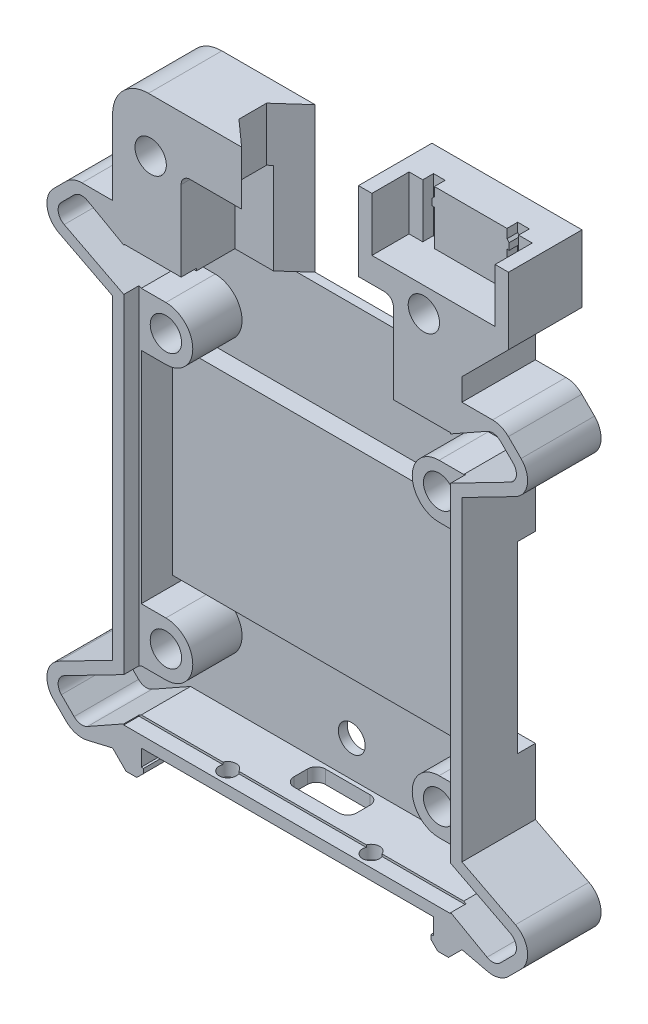
SolidWorks part; units mm, degrees
ref_plane "Front Plane" through (0, 0, 0) normal (0, 0, 1) x (1, 0, 0)
ref_plane "Top Plane" through (0, 0, 0) normal (0, 1, 0) x (1, 0, 0)
ref_plane "Right Plane" through (0, 0, 0) normal (1, 0, 0) x (0, 0, -1)
sketch "Sketch1" plane through (0, 0, 0) normal (0, 0, 1) x (1, 0, 0)
  line L0 (15.25, -20.35) -> (18, -20.35)
  line L1 (-19.5, -32.6) -> (19.5, -32.6)
  line L2 (-19.5, -32.6) -> (-19.5, 31.1)
  line L3 (-19.5, 31.1) -> (19.5, 31.1)
  line L4 (19.5, -32.6) -> (19.5, 31.1)
  line L5 (-15.25, -20.35) -> (-18, -20.35)
  line L6 (15.25, -26.35) -> (18, -26.35)
  line L7 (6.95, 31.1) -> (-15.5, 31.1) construction
  line L8 (-18, -31.1) -> (-18, 29.6)
  line L9 (-18, 29.6) -> (18, 29.6)
  line L10 (18, -31.1) -> (18, 29.6)
  line L11 (-18, -31.1) -> (18, -31.1)
  line L12 (-18, 14.9) -> (18, 14.9)
  line L13 (7.85, 14.9) -> (-4.95, 14.9) construction
  line L14 (-15.25, 4.15) -> (-18, 4.15)
  line L15 (-15.25, 10.15) -> (-18, 10.15)
  line L16 (15.25, 10.15) -> (18, 10.15)
  line L17 (15.25, 4.15) -> (18, 4.15)
  line L18 (-15.25, -26.35) -> (-18, -26.35)
  line L19 (19.5, -32.6) -> (19.5, -18.35) construction
  line L20 (-19.5, -32.6) -> (-19.5, -18.35) construction
  line L21 (19.5, -32.6) -> (-19.5, -32.6) construction
  line L22 (0, 31.1) -> (0, -32.6) construction
  line L23 (9.45, 26.9) -> (24.7, 26.9)
  line L24 (9.45, 26.9) -> (9.45, 33.9)
  line L25 (9.45, 33.9) -> (24.7, 33.9)
  line L26 (24.7, 26.9) -> (24.7, 33.9)
  line L27 (18, 29.6) -> (19.5, 31.1) construction
  line L28 (18.75, 30.35) -> (0, 30.35) construction
  line L29 (9.45, 26.9) -> (7.95, 26.9) construction
  line L30 (-7.95, 31.1) -> (7.95, 31.1)
  line L31 (-7.95, 31.1) -> (-7.95, 29.6)
  line L32 (-7.95, 29.6) -> (7.95, 29.6)
  line L33 (7.95, 31.1) -> (7.95, 29.6)
  line L34 (-7.95, 31.1) -> (7.95, 29.6) construction
  line L35 (-7.95, 29.6) -> (7.95, 31.1) construction
  line L36 (7.95, 26.9) -> (7.95, 29.6) construction
  line L37 (18, 29.6) -> (19.5, 29.6) construction
  line L38 (24.7, 26.4) -> (19.5, 21.2)
  line L39 (9.45, 33.9) -> (7.95, 33.9)
  line L40 (23.2, 33.9) -> (23.2, 26.9)
  line L41 (7.95, 33.9) -> (7.95, 31.1)
  line L42 (24.7, 30.4) -> (23.2, 30.4) construction
  line L43 (24.7, 26.9) -> (19.5, 26.9)
  line L44 (24.7, 26.9) -> (24.7, 26.4)
  line L45 (24.7, 26.4) -> (19.5, 26.4)
  line L46 (19.5, 26.9) -> (19.5, 26.4)
  circle A0 centre (15.25, -23.35) radius 1.75
  arc A1 (-15.5, 31.1) -> (-19.5, 27.1) centre (-15.5, 27.1) ccw construction
  circle A2 centre (15.25, -23.35) radius 3
  arc A3 (-15.5, 31.1) -> (-19.5, 27.1) centre (-15.5, 27.1) ccw
  arc A4 (-15.5, 29.6) -> (-18, 27.1) centre (-15.5, 27.1) ccw
  circle A6 centre (-15.25, -23.35) radius 1.75
  circle A7 centre (-15.25, -23.35) radius 1.75
  circle A8 centre (-15.25, 7.15) radius 1.75
  circle A9 centre (15.25, 7.15) radius 1.75
  circle A10 centre (15.25, 25.15) radius 1.75
  circle A11 centre (-15.25, 25.15) radius 1.75
  circle A12 centre (-15.25, -23.35) radius 3
  circle A13 centre (-15.25, -23.35) radius 3
  circle A14 centre (15.25, 7.15) radius 3
  circle A15 centre (-15.25, 7.15) radius 3
  dimension "D2" = 1.5
  dimension "D4" = 6
  dimension "D3" = 3.5
  dimension "D5" = 13.75
  dimension "D6" = 15.9
  dimension "D7" = 7
  dimension "D8" = 45
  dimension "D9" = 0.5
  dimension "D1" = 1.5
extrude "Base shape" add sketch "Sketch1" along normal up to surface (8.2 mm away) contours A15 L8 L9 L31 L3 A3 L2 L1 L4 L23 L10 A14 A2 L11 A12 | A12 L8 L18 | A12 L8 A6 | L8 A12 | A12 L5 L8 | A15 L8 L14 | A15 L8 A8 | L8 A15 | A15 L15 L8 | L23 A10 L24 L9 A4 L8 L12 L10 A11 | A4 L9 L8 | L33 L3 L31 L9 | L3 L33 L9 L24 | L24 L9 L10 L23 L4 L3 | L24 L23 L10 L9 | A14 L10 L16 | L10 A14 A9 | A14 L17 L10 | L10 A14 | L10 A2 L6 | A2 L10 A0 | L0 A2 L10 | A2 L10 | L40 L25 L24 L3 L4 L23 | L25 L40 L23 L26 | L38 L45 L4 | L45 L44 L23 L4 | L39 L41 L3 L24 region at (16.8481, -20.9099, 0) region at (17.3601, -20.8437, 0) region at (18.7469, -8.1, 0) region at (17.3601, -25.8563, 0) region at (18.1004, -23.35, 0) region at (17.3601, 4.6437, 0) region at (16.8481, 4.7099, 0) region at (18.1004, 7.15, 0) region at (17.3601, 9.6563, 0) region at (-17.3601, -25.8563, 0) region at (-0.6044, 21.831, 0) region at (-18.1004, -23.35, 0) region at (-17.9169, -23.35, 0) region at (13.725, 28.25, 0) region at (15.3803, 29.9053, 0) region at (-17.3601, -20.8437, 0) region at (22.1, 26.65, 0) region at (17.77, 31.4935, 0) region at (-17.3601, 9.6563, 0) region at (-17.4416, 29.0416, 0) region at (8.7, 30.35, 0) region at (21.2333, 24.6667, 0) region at (23.95, 30.4, 0) region at (-16.8481, 9.5901, 0) region at (-18.1004, 7.15, 0) region at (-17.3601, 4.6437, 0) region at (0, 30.35, 0) region at (8.7, 32.5, 0)
sketch "Sketch3" plane through (19.5, 0, 0) normal (1, 0, 0) x (0, 0, -1)
  line L1 (0, -18.35) -> (-2, -18.35)
  line L2 (0, -18.35) -> (0, 2.15)
  line L3 (0, 2.15) -> (-2, 2.15)
  line L4 (-2, -18.35) -> (-2, 2.15)
  line L5 (0, -18.35) -> (1.75, -18.35) construction
  line L6 (0, 2.15) -> (1.75, 2.15) construction
  line L7 (0, -32.6) -> (0, 21.2) construction
  dimension "D1" = 2
extrude "Strap cut" cut sketch "Sketch3" against normal through all
sketch "Sketch4" plane through (0, 31.1, 0) normal (0, 1, 0) x (1, 0, 0)
  line L2 (7.95, 0) -> (-5.0998, 0)
  line L4 (-15.5, 0) -> (7.95, 0) construction
  line L5 (-15.5, -8.2) -> (7.95, -8.2) construction
  line L6 (7.95, -8.2) -> (-5.0998, -8.2)
  line L12 (7.95, -8.3) -> (7.95, 0.1)
  line L13 (7.95, 0.1) -> (-4.9883, 0.1)
  line L14 (-4.9883, 0.1) -> (-7.95, -2.5553)
  line L15 (-7.95, -2.5553) -> (-7.95, -5.6447)
  line L16 (-7.95, -5.6447) -> (-4.9883, -8.3)
  line L17 (-4.9883, -8.3) -> (7.95, -8.3)
  line L18 (7.95, -8.3) -> (7.95, 0.1)
  line L19 (7.95, 0.1) -> (-4.9883, 0.1)
  line L20 (-4.9883, 0.1) -> (-7.95, -2.5553)
  line L21 (-7.95, -2.5553) -> (-7.95, -5.6447)
  line L22 (-7.95, -5.6447) -> (-4.9883, -8.3)
  line L23 (-4.9883, -8.3) -> (7.95, -8.3)
  dimension "D1" = 0.1
extrude "XT60 cut" cut sketch "Sketch4" against normal up to next contours L21 L22 L18 L20 region at (0.4142, 31.1, 4.1)
sketch "Sketch6" plane through (0, 0, 8.2) normal (0, 0, 1) x (1, 0, 0)
  line L0 (8.85, 14.9) -> (10.85, 14.9) construction
  line L1 (11.85, 24.1) -> (11.85, 15.9) construction
  line L3 (-11.85, 14.9) -> (11.85, 14.9)
  line L4 (-11.85, 24.1) -> (-11.85, 15.9) construction
  line L5 (11.85, 24.1) -> (11.85, 15.9)
  line L6 (10.85, 25.1) -> (-10.85, 25.1)
  line L7 (-11.85, 24.1) -> (-11.85, 15.9)
  line L8 (-11.85, 15.9) -> (-11.85, 14.9)
  line L9 (11.85, 15.9) -> (11.85, 14.9)
  arc A2 (-10.85, 25.1) -> (-11.85, 24.1) centre (-10.85, 24.1) ccw construction
  arc A3 (-10.85, 25.1) -> (-11.85, 24.1) centre (-10.85, 24.1) ccw
  arc A4 (11.85, 24.1) -> (10.85, 25.1) centre (10.85, 24.1) ccw construction
  arc A5 (11.85, 24.1) -> (10.85, 25.1) centre (10.85, 24.1) ccw
  line M1 (7.95, 33.9) -> (7.95, 14.9)
  line M15 (-5.0998, 14.9) -> (-5.0998, 31.1)
  line M118 (7.95, 14.9) -> (18, 14.9)
  line M134 (-18, 14.9) -> (-5.0998, 14.9)
extrude "IO wires cut" cut sketch "Sketch6" against normal blind 6 contours L7 L8 M134 M15 | L3 M15 M1 | L5 L9 M1 M118 region at (-8.465, 19.9848, 8.2) region at (1.4251, 20, 8.2) region at (9.8906, 19.9735, 8.2)
sketch "Sketch7" plane through (-18, 0, 0) normal (1, 0, 0) x (0, 0, -1)
  line L6 (0, -18.35) -> (0, -20.35)
  line L7 (-2, -18.35) -> (0, -18.35)
  line L8 (-2, 2.15) -> (-2, -18.35)
  line L9 (0, 2.15) -> (-2, 2.15)
  line L12 (0, 3.15) -> (-3, 3.15)
  line L13 (-3, 3.15) -> (-3, -19.35)
  line L14 (-3, -19.35) -> (-1, -19.35)
  line L15 (-1, -19.35) -> (-1, -20.35)
  line L16 (-1, -20.35) -> (0, -20.35)
  line L17 (0, 3.15) -> (-1, 3.15)
  line L19 (0, -31.1) -> (-1, -31.1)
  line L22 (0, -31.1) -> (0, -20.35)
  line L23 (0, -20.35) -> (-1, -20.35)
  line L24 (-1, -31.1) -> (-1, -20.35)
  line L25 (0, 3.15) -> (0, 14.9)
  line L26 (0, 14.9) -> (-1, 14.9)
  line L27 (-1, 3.15) -> (-1, 14.9)
  line L28 (-8.2, 14.9) -> (0, 14.9) construction
  line L31 (0, -20.35) -> (0, -18.35) construction
  line L32 (0, 2.15) -> (-2, 2.15) construction
  line M48 (0, -20.35) -> (0, -18.35)
  line M49 (0, -18.35) -> (-2, -18.35)
  line M50 (-2, -18.35) -> (-2, 2.15)
  line M51 (-2, 2.15) -> (0, 2.15)
  line M52 (0, 2.15) -> (0, 4.15)
  line M53 (0, 4.15) -> (-8.2, 4.15)
  line M55 (-8.2, -20.35) -> (0, -20.35)
  dimension "D1" = 1
extrude "Bottom" add sketch "Sketch7" along normal up to surface (36 mm away) contours L27 L25 L26 M53 | L27 L12 M52 M53 | L14 L15 L12 L13 M55 M48 M49 M50 M51 M52 | L24 L19 L22 M55 region at (-18, -8.5273, 2.2091) region at (-18, -25.725, 0.5) region at (-18, 3.65, 0.5) region at (-18, 9.525, 0.5) up to face at (18, -8.1, 2.55)
sketch "Sketch9" plane through (0, 0, 0) normal (0, 0, -1) x (-1, 0, 0)
  circle A0 centre (15.25, -23.35) radius 1.75 construction
  circle A1 centre (-15.25, 7.15) radius 1.75 construction
  circle A2 centre (15.25, 7.15) radius 1.75 construction
  circle A3 centre (15.25, -23.35) radius 1.75 construction
  circle A4 centre (15.25, -23.35) radius 1.75
  circle A5 centre (-15.25, 7.15) radius 1.75
  circle A6 centre (15.25, 7.15) radius 1.75
  circle A7 centre (15.25, -23.35) radius 1.75
  circle A8 centre (-15.25, -23.35) radius 1.75 construction
  circle A9 centre (-15.25, -23.35) radius 1.75
extrude "Bottom holes" cut sketch "Sketch9" against normal up to next contours A5 | A6 | A4 | A9 region at (-15.25, -23.35, 0) region at (15.25, 7.15, 0) region at (-15.25, 7.15, 0) region at (15.25, -23.35, 0)
sketch "Sketch8" plane through (0, 0, 8.2) normal (0, 0, 1) x (1, 0, 0)
  line L1 (-18, 14.9) -> (18, -31.1) construction
  line L3 (-18.25, -31.35) -> (18.25, -31.35)
  line L4 (-18.25, -31.35) -> (-18.25, 15.15)
  line L5 (-18.25, 15.15) -> (18.25, 15.15)
  line L6 (18.25, -31.35) -> (18.25, 15.15)
  line L7 (-18.25, -31.35) -> (18.25, 15.15) construction
  line L8 (-18.25, 15.15) -> (18.25, -31.35) construction
  line L10 (-18, 10.15) -> (-18, 14.9) construction
  line L11 (-18, 14.9) -> (-18.25, 14.9) construction
  line L12 (-18, 14.9) -> (-18, 15.15) construction
  point P2 (0, -8.1)
  point P7 (0, 0)
  dimension "D1" = 0.25
extrude "PCB cut" cut sketch "Sketch8" against normal blind 1.7
sketch "Sketch11" plane through (0, -32.6, 0) normal (0, -1, 0) x (1, 0, 0)
  line L0 (19.5, 8.2) -> (19.5, 0) construction
  line L1 (-19.5, 8.2) -> (19.5, 8.2)
  line L2 (-19.5, 8.2) -> (-19.5, -1.8)
  line L3 (-19.5, -1.8) -> (19.5, -1.8)
  line L4 (19.5, 8.2) -> (19.5, -1.8)
  line L5 (-19.5, 3.2) -> (19.5, 3.2) construction
  line L6 (0, -1.8) -> (0, 8.2) construction
  line L8 (-2.5, 4.95) -> (2.5, 4.95)
  line L9 (-3.5, 3.95) -> (-3.5, 2.45)
  line L10 (-2.5, 1.45) -> (2.5, 1.45)
  line L11 (3.5, 3.95) -> (3.5, 2.45)
  line L12 (-3.5, 4.95) -> (3.5, 1.45) construction
  line L13 (-3.5, 1.45) -> (3.5, 4.95) construction
  arc A0 (2.5, 4.95) -> (3.5, 3.95) centre (2.5, 3.95) cw
  arc A1 (2.5, 1.45) -> (3.5, 2.45) centre (2.5, 2.45) ccw
  arc A2 (-3.5, 2.45) -> (-2.5, 1.45) centre (-2.5, 2.45) ccw
  arc A3 (-2.5, 4.95) -> (-3.5, 3.95) centre (-2.5, 3.95) ccw
  point P11 (0, 3.2)
  dimension "D4" = 1
  dimension "D1" = 10
  dimension "D2" = 7
  dimension "D3" = 3.5
extrude "Ledbar wires cut" cut sketch "Sketch11" against normal up to next contours L8 A3 L9 A2 L10 A1 L11 A0 region at (0, -32.6, 3.2)
sketch "Sketch13" plane through (0, -32.6, 0) normal (0, -1, 0) x (1, 0, 0)
  line L0 (-19.5, 8.2) -> (19.5, 8.2) construction
  line L1 (19.5, 0) -> (16.3, 0)
  line L2 (19.5, 0) -> (19.5, 8.2)
  line L3 (19.5, 8.2) -> (16.3, 8.2)
  line L4 (16.3, 0) -> (16.3, 8.2)
  line L5 (16.1, -1.8) -> (16.1, 8.2) construction
  line L6 (0, 8.2) -> (0, 0) construction
  line L7 (-19.5, 0) -> (-16.3, 0)
  line L8 (-19.5, 0) -> (-19.5, 8.2)
  line L9 (-19.5, 8.2) -> (-16.3, 8.2)
  line L10 (-16.3, 0) -> (-16.3, 8.2)
  dimension "D1" = 0.2
extrude "Ledbar sides" add sketch "Sketch13" along normal blind 1.6
sketch "Sketch16" plane through (0, 33.9, 0) normal (0, 1, 0) x (1, 0, 0)
  line L0 (7.95, -6.125) -> (24.7, -6.125) construction
  line L1 (7.95, -8.2) -> (24.7, -8.2) construction
  line L2 (21.675, -2.85) -> (20.375, -2.85)
  line L3 (20.375, -4.05) -> (20.375, -2.85)
  line L4 (9.45, -4.05) -> (23.2, -4.05)
  line L5 (9.45, -4.05) -> (9.45, -8.2)
  line L6 (9.45, -8.2) -> (23.2, -8.2)
  line L7 (23.2, -4.05) -> (23.2, -8.2)
  line L8 (9.45, -4.05) -> (23.2, -8.2) construction
  line L9 (9.45, -8.2) -> (23.2, -4.05) construction
  line L10 (24.7, -8.2) -> (24.7, 0) construction
  line L11 (7.95, -8.2) -> (7.95, 0) construction
  line L12 (16.325, -8.2) -> (16.325, -4.05) construction
  line L13 (11.625, -2.85) -> (11.625, -4.05) construction
  line L14 (10.975, -4.05) -> (12.275, -4.05)
  line L15 (10.975, -4.05) -> (10.975, -2.85)
  line L16 (10.975, -2.85) -> (12.275, -2.85)
  line L17 (12.275, -4.05) -> (12.275, -2.85)
  line L18 (10.975, -2.85) -> (10.975, -8.2) construction
  line L19 (21.675, -4.05) -> (21.675, -2.85)
  point P6 (16.325, -6.125)
  dimension "D1" = 13.75
  dimension "D2" = 4.15
  dimension "D3" = 1.3
  dimension "D4" = 1.2
  dimension "D5" = 4.7
extrude "Balance plug cut" cut sketch "Sketch16" against normal blind 6 contours L7 L4 L5 L6 | L4 L17 L16 L15 | L4 L19 L2 L3 region at (21.025, 33.9, 3.45) region at (16.325, 33.9, 6.125) region at (11.625, 33.9, 3.45)
sketch "Sketch17" plane through (0, 0, 2.85) normal (0, 0, 1) x (1, 0, 0)
  line L0 (16.325, 33.9) -> (16.325, 27.9) construction
  line L1 (12.275, 33.9) -> (20.375, 33.9) construction
  line L2 (12.275, 27.9) -> (20.375, 27.9) construction
  line L3 (12.275, 27.9) -> (12.275, 33.9) construction
  line L4 (12.025, 32.9) -> (20.625, 32.9)
  line L5 (12.025, 32.9) -> (12.025, 31.9)
  line L6 (12.025, 31.9) -> (20.625, 31.9)
  line L7 (20.625, 32.9) -> (20.625, 31.9)
  line L8 (12.025, 32.9) -> (20.625, 31.9) construction
  line L9 (12.025, 31.9) -> (20.625, 32.9) construction
  line L10 (12.025, 32.65) -> (12.275, 32.9)
  line L11 (20.625, 32.65) -> (20.375, 32.9)
  point P6 (16.325, 32.4)
  line M7 (20.375, 33.9) -> (20.375, 27.9)
  dimension "D1" = 0.25
  dimension "D2" = 1
  dimension "D3" = 1
  dimension "D4" = 45
extrude "Balance plug locks" add sketch "Sketch17" along normal up to surface (1.2 mm away) contours L10 L5 L6 L4 M7 | L7 L11 L6 M7 region at (16.2154, 32.3984, 2.85) region at (20.494, 32.3405, 2.85) up to face at (16.325, 30.9, 4.05)
sketch "Sketch18" plane through (0, 0, 0) normal (0, 0, -1) x (-1, 0, 0)
  line L0 (0, -32.6) -> (0, -18.35) construction
  line L1 (16.3, -32.6) -> (-16.3, -32.6) construction
  line L2 (19.5, -18.35) -> (-19.5, -18.35) construction
  line L3 (-19.5, -28.6) -> (19.5, -28.6) construction
  line L4 (-19.5, -34.2) -> (-19.5, -18.35) construction
  line L5 (19.5, -34.2) -> (19.5, -18.35) construction
  circle A0 centre (0, -27.1) radius 1.5
  dimension "D2" = 3
  dimension "D1" = 4
extrude "PDB removal hole" cut sketch "Sketch18" against normal up to next
sketch "Sketch14" plane through (0, -32.6, 0) normal (0, -1, 0) x (1, 0, 0)
  circle A0 centre (8, 6.85) radius 0.95
  circle A1 centre (-8, 6.85) radius 0.95
  dimension "D1" = 1.9
extrude "Ledbar holes" cut sketch "Sketch14" against normal up to next
sketch "Sketch10" plane through (0, 0, 2) normal (0, 0, -1) x (-1, 0, 0)
  line L0 (0, 2.15) -> (0, -18.35) construction
  line L1 (19.5, 2.15) -> (-19.5, 2.15) construction
  line L2 (19.5, -18.35) -> (-19.5, -18.35) construction
  line L3 (19.5, 2.15) -> (19.5, -18.35) construction
  line L4 (-19.5, 1.15) -> (19.5, 1.15)
  line L5 (-19.5, 1.15) -> (-19.5, 0.65)
  line L6 (-19.5, 0.65) -> (19.5, 0.65)
  line L7 (19.5, 1.15) -> (19.5, 0.65)
  line L8 (-19.5, 1.15) -> (19.5, 0.65) construction
  line L9 (-19.5, 0.65) -> (19.5, 1.15) construction
  line L10 (-19.5, 2.15) -> (19.5, 2.15) construction
  line L11 (-19.5, -1.35) -> (19.5, -1.35)
  line L12 (19.5, -0.85) -> (19.5, -1.35)
  line L13 (-19.5, -0.85) -> (19.5, -0.85)
  line L14 (-19.5, -0.85) -> (-19.5, -1.35)
  line L15 (-19.5, -3.35) -> (19.5, -3.35)
  line L16 (19.5, -2.85) -> (19.5, -3.35)
  line L17 (-19.5, -2.85) -> (19.5, -2.85)
  line L18 (-19.5, -2.85) -> (-19.5, -3.35)
  line L19 (-19.5, -5.35) -> (19.5, -5.35)
  line L20 (19.5, -4.85) -> (19.5, -5.35)
  line L21 (-19.5, -4.85) -> (19.5, -4.85)
  line L22 (-19.5, -4.85) -> (-19.5, -5.35)
  line L23 (-19.5, -7.35) -> (19.5, -7.35)
  line L24 (19.5, -6.85) -> (19.5, -7.35)
  line L25 (-19.5, -6.85) -> (19.5, -6.85)
  line L26 (-19.5, -6.85) -> (-19.5, -7.35)
  line L27 (-19.5, -9.35) -> (19.5, -9.35)
  line L28 (19.5, -8.85) -> (19.5, -9.35)
  line L29 (-19.5, -8.85) -> (19.5, -8.85)
  line L30 (-19.5, -8.85) -> (-19.5, -9.35)
  line L31 (-19.5, -11.35) -> (19.5, -11.35)
  line L32 (19.5, -10.85) -> (19.5, -11.35)
  line L33 (-19.5, -10.85) -> (19.5, -10.85)
  line L34 (-19.5, -10.85) -> (-19.5, -11.35)
  line L35 (-19.5, -13.35) -> (19.5, -13.35)
  line L36 (19.5, -12.85) -> (19.5, -13.35)
  line L37 (-19.5, -12.85) -> (19.5, -12.85)
  line L38 (-19.5, -12.85) -> (-19.5, -13.35)
  line L39 (-19.5, -15.35) -> (19.5, -15.35)
  line L40 (19.5, -14.85) -> (19.5, -15.35)
  line L41 (-19.5, -14.85) -> (19.5, -14.85)
  line L42 (-19.5, -14.85) -> (-19.5, -15.35)
  line L43 (-19.5, -17.35) -> (19.5, -17.35)
  line L44 (19.5, -16.85) -> (19.5, -17.35)
  line L45 (-19.5, -16.85) -> (19.5, -16.85)
  line L46 (-19.5, -16.85) -> (-19.5, -17.35)
  point P6 (0, 0.9)
  dimension "D1" = 1
  dimension "D2" = 0.5
  dimension "D4" = 2
  dimension "D3" = 10
extrude "3D print ribs" [suppressed] add sketch "Sketch10" along normal up to surface (2 mm away) up to face at (-17, 7.15, 0)
sketch "Sketch22" plane through (0, 0, 0) normal (0, 0, -1) x (-1, 0, 0)
  line L0 (22.918, 18.7322) -> (19.5, 18.7322)
  line L1 (19.5, -34.2) -> (19.5, 27.1) construction
  line L2 (19.5, -25.7166) -> (25.4771, -28.7956)
  line L3 (-23.4483, 13.9341) -> (-22.0341, 15.3483)
  line L4 (-23.8019, 17.1161) -> (-25.2161, 15.7019)
  line L5 (-23.4483, 13.9341) -> (-22.0341, 15.3483)
  line L6 (-23.8019, 17.1161) -> (-25.2161, 15.7019)
  line L7 (-22.5645, 13.0503) -> (-21.1503, 14.4645)
  line L8 (-25.2161, -31.9019) -> (-23.8019, -33.3161)
  line L9 (-22.0341, -31.5483) -> (-23.4483, -30.1341)
  line L10 (-25.2161, -31.9019) -> (-23.8019, -33.3161)
  line L11 (-22.0341, -31.5483) -> (-23.4483, -30.1341)
  line L12 (-24.6858, 18) -> (-26.1, 16.5858)
  line L13 (22.0341, 15.3483) -> (23.4483, 13.9341)
  line L14 (25.2161, 15.7019) -> (23.8019, 17.1161)
  line L15 (22.0341, 15.3483) -> (23.4483, 13.9341)
  line L16 (25.2161, 15.7019) -> (23.8019, 17.1161)
  line L17 (23.8019, -33.3161) -> (25.2161, -31.9019)
  line L18 (23.4483, -30.1341) -> (22.0341, -31.5483)
  line L19 (23.8019, -33.3161) -> (25.2161, -31.9019)
  line L20 (23.4483, -30.1341) -> (22.0341, -31.5483)
  line L21 (26.1, 16.5858) -> (24.6858, 18)
  line L22 (21.1503, 14.4645) -> (22.5645, 13.0503)
  line L23 (22.5645, -29.2503) -> (21.1503, -30.6645)
  line L24 (24.6858, -34.2) -> (26.1, -32.7858)
  line L25 (-21.1503, -30.6645) -> (-22.5645, -29.2503)
  line L26 (-26.1, -32.7858) -> (-24.6858, -34.2)
  line L27 (-19.5, 18.7322) -> (-22.918, 18.7322)
  line L28 (-19.5, -34.2) -> (-19.5, 21.2) construction
  line L29 (18, 10.15) -> (24.9047, 13.7068) construction
  line L30 (-19.5, -34.2) -> (-22.3484, -34.8665)
  line L31 (-19.5, -25.7166) -> (-25.4771, -28.7956)
  line L32 (19.5, 18.7322) -> (19.5, 9.5166)
  line L33 (19.5, -34.2) -> (22.3484, -34.8665)
  line L35 (24.9047, -29.9068) -> (18, -26.35) construction
  line L37 (-19.5, 9.5166) -> (-25.4771, 12.5956)
  line L38 (19.5, 9.5166) -> (25.4771, 12.5956)
  line L39 (-19.5, 18.7322) -> (-19.5, 9.5166)
  line L40 (-19.5, -25.7166) -> (-19.5, -34.2)
  line L41 (19.5, -25.7166) -> (19.5, -34.2)
  arc A0 (-26.1, 16.5858) -> (-22.5645, 13.0503) centre (-24.3322, 14.818) ccw
  arc A1 (-21.1503, 14.4645) -> (-24.6858, 18) centre (-22.918, 16.2322) ccw
  arc A2 (-22.0341, 15.3483) -> (-23.8019, 17.1161) centre (-22.918, 16.2322) ccw
  arc A3 (-25.2161, 15.7019) -> (-23.4483, 13.9341) centre (-24.3322, 14.818) ccw
  arc A4 (-22.0341, 15.3483) -> (-23.8019, 17.1161) centre (-22.918, 16.2322) ccw
  arc A5 (-25.2161, 15.7019) -> (-23.4483, 13.9341) centre (-24.3322, 14.818) ccw
  arc A6 (-23.4483, -30.1341) -> (-25.2161, -31.9019) centre (-24.3322, -31.018) ccw
  arc A7 (-23.8019, -33.3161) -> (-22.0341, -31.5483) centre (-22.918, -32.4322) ccw
  arc A8 (-23.4483, -30.1341) -> (-25.2161, -31.9019) centre (-24.3322, -31.018) ccw
  arc A9 (-23.8019, -33.3161) -> (-22.0341, -31.5483) centre (-22.918, -32.4322) ccw
  arc A10 (23.4483, 13.9341) -> (25.2161, 15.7019) centre (24.3322, 14.818) ccw
  arc A11 (23.8019, 17.1161) -> (22.0341, 15.3483) centre (22.918, 16.2322) ccw
  arc A12 (23.4483, 13.9341) -> (25.2161, 15.7019) centre (24.3322, 14.818) ccw
  arc A13 (23.8019, 17.1161) -> (22.0341, 15.3483) centre (22.918, 16.2322) ccw
  arc A14 (25.2161, -31.9019) -> (23.4483, -30.1341) centre (24.3322, -31.018) ccw
  arc A15 (22.0341, -31.5483) -> (23.8019, -33.3161) centre (22.918, -32.4322) ccw
  arc A16 (25.2161, -31.9019) -> (23.4483, -30.1341) centre (24.3322, -31.018) ccw
  arc A17 (22.0341, -31.5483) -> (23.8019, -33.3161) centre (22.918, -32.4322) ccw
  arc A18 (22.5645, 13.0503) -> (26.1, 16.5858) centre (24.3322, 14.818) ccw
  arc A19 (24.6858, 18) -> (21.1503, 14.4645) centre (22.918, 16.2322) ccw
  arc A20 (26.1, -32.7858) -> (22.5645, -29.2503) centre (24.3322, -31.018) ccw
  arc A21 (21.1503, -30.6645) -> (24.6858, -34.2) centre (22.918, -32.4322) ccw
  arc A22 (-24.6858, -34.2) -> (-21.1503, -30.6645) centre (-22.918, -32.4322) ccw
  arc A23 (-22.5645, -29.2503) -> (-26.1, -32.7858) centre (-24.3322, -31.018) ccw
  point P65 (0, 0)
  dimension "D1" = 0
  dimension "D2" = 0
  dimension "D3" = 0
  dimension "D4" = 0
  dimension "D5" = 1.25
extrude "ESC wire tunnels" add sketch "Sketch22" against normal up to surface (8.2 mm away) contours A19 L0 A18 L22 | L21 A19 L22 A18 A13 L16 A12 L15 | A1 L12 A0 L7 A5 L6 A4 L5 | A1 L7 A0 L27 | A21 L23 A20 L33 | L23 A21 L24 A20 A17 L20 A16 L19 | A23 L25 A22 L30 | L25 A23 L26 A22 A9 L10 A8 L11 | L16 A13 L15 A12 | L6 A5 L5 A4 | L10 A9 L11 A8 | L20 A17 L19 A16 region at (-20.9045, 13.5633, 0) region at (-23.84, 18.4581, 0) region at (-20.927, -29.4513, 0) region at (-26.7127, -30.6464, 0) region at (23.6251, 15.5251, 0) region at (23.9606, 12.4376, 0) region at (20.9045, 13.5633, 0) region at (23.6251, -31.7251, 0) region at (-23.6251, 15.5251, 0) region at (-23.6251, -31.7251, 0) region at (20.6011, -33.0929, 0) region at (20.927, -29.4513, 0) up to face at (17, 25.15, 8.2)
sketch "Sketch23" plane through (0, 0, 8.2) normal (0, 0, 1) x (1, 0, 0)
  line L46 (-18, 14.9) -> (-22.3052, 17.3217)
  line L47 (-18, 10.15) -> (-18.9276, 10.6278)
  line L48 (-18, 14.9) -> (-18, 10.15)
  line L49 (-18.9276, 10.6278) -> (-24.9047, 13.7068)
  line L50 (-25.2161, 15.7019) -> (-23.8019, 17.1161)
  line L51 (-22.918, 17.4822) -> (-19.5, 17.4822)
  line L52 (-18.9276, 10.6278) -> (-24.9047, 13.7068)
  line L53 (-25.2161, 15.7019) -> (-23.8019, 17.1161)
  line L54 (-22.918, 17.4822) -> (-19.5, 17.4822)
  line L58 (-18, -31.1) -> (-22.3052, -33.5217)
  line L59 (-18.9276, -26.8278) -> (-18, -26.35)
  line L60 (-18, -26.35) -> (-18, -31.1)
  line L61 (-22.6332, -33.6494) -> (-19.7848, -32.9829)
  line L62 (-25.2161, -31.9019) -> (-23.8019, -33.3161)
  line L63 (-18.9276, -26.8278) -> (-24.9047, -29.9068)
  line L64 (-22.6332, -33.6494) -> (-19.7848, -32.9829)
  line L65 (-25.2161, -31.9019) -> (-23.8019, -33.3161)
  line L66 (-18.9276, -26.8278) -> (-24.9047, -29.9068)
  line L67 (0, -6.351) -> (0, 7.9246) construction
  line L68 (18, -26.35) -> (18, -31.1)
  line L69 (18, -31.1) -> (22.3052, -33.5217)
  line L70 (25.2161, -31.9019) -> (23.8019, -33.3161)
  line L71 (18.9276, -26.8278) -> (24.9047, -29.9068)
  line L72 (18.9276, -26.8278) -> (18, -26.35)
  line L73 (18, 10.15) -> (18.9276, 10.6278)
  line L74 (18.9276, 10.6278) -> (24.9047, 13.7068)
  line L75 (25.2161, 15.7019) -> (23.8019, 17.1161)
  line L76 (18, 14.9) -> (22.3052, 17.3217)
  line L77 (18, 14.9) -> (18, 10.15)
  circle A30 centre (-22.918, 16.2322) radius 1.25
  arc A32 (-25.2161, 15.7019) -> (-24.9047, 13.7068) centre (-24.3322, 14.818) ccw
  arc A33 (-22.918, 17.4822) -> (-23.8019, 17.1161) centre (-22.918, 16.2322) ccw
  arc A34 (-25.2161, 15.7019) -> (-24.9047, 13.7068) centre (-24.3322, 14.818) ccw
  arc A35 (-22.918, 17.4822) -> (-23.8019, 17.1161) centre (-22.918, 16.2322) ccw
  circle A37 centre (-22.918, -32.4322) radius 1.25
  circle A38 centre (22.918, -32.4322) radius 1.25
  arc A39 (-23.8019, -33.3161) -> (-22.6332, -33.6494) centre (-22.918, -32.4322) ccw
  arc A40 (-24.9047, -29.9068) -> (-25.2161, -31.9019) centre (-24.3322, -31.018) ccw
  arc A41 (-23.8019, -33.3161) -> (-22.6332, -33.6494) centre (-22.918, -32.4322) ccw
  arc A42 (-24.9047, -29.9068) -> (-25.2161, -31.9019) centre (-24.3322, -31.018) ccw
  arc A43 (24.9047, -29.9068) -> (25.2161, -31.9019) centre (24.3322, -31.018) cw
  arc A44 (25.2161, 15.7019) -> (24.9047, 13.7068) centre (24.3322, 14.818) cw
  circle A45 centre (22.918, 16.2322) radius 1.25
  dimension "D1" = 1.25
  dimension "D2" = 1.25
extrude "Cut-Extrude5" cut sketch "Sketch23" against normal up to surface (7.2 mm away) contours L74 | L53 A34 L52 L47 L48 L46 A30 | A30 | L75 A45 L76 L77 L73 L74 A44 | A45 | A37 | L66 A42 L65 A37 L58 L60 L59 | A43 L71 L72 L68 L69 A38 L70 | A38 region at (-21.1189, 13.7975, 8.2) region at (-22.918, 16.2322, 8.2) region at (-21.1189, -29.9975, 8.2) region at (-22.918, -32.4322, 8.2) region at (21.1189, -29.9975, 8.2) region at (22.918, -32.4322, 8.2) region at (21.1189, 13.7975, 8.2) region at (22.918, 16.2322, 8.2) up to face at (0.1239, 8.7929, 1)
sketch "Sketch24" plane through (0, 0, 8.2) normal (0, 0, 1) x (1, 0, 0)
  line L0 (0, -4.5098) -> (0, 6.2776) construction
  line L1 (-16.3, -34.2) -> (-19.5, -34.2) construction
  line L2 (19.5, -35.7) -> (-19.5, -35.7)
  line L3 (19.5, -35.7) -> (19.5, -34.2)
  line L4 (19.5, -34.2) -> (-19.5, -34.2)
  line L5 (-19.5, -35.7) -> (-19.5, -34.2)
  line L6 (19.5, -35.7) -> (-19.5, -34.2) construction
  line L7 (19.5, -34.2) -> (-19.5, -35.7) construction
  line L8 (-16.3, -34.2) -> (-16.3, -32.6) construction
  line L9 (-16.3, -34.2) -> (-16.3, -35.7)
  line L10 (16.05, -35.7) -> (-16.05, -35.7)
  line L11 (16.05, -35.7) -> (16.05, -34.2)
  line L12 (16.05, -34.2) -> (-16.05, -34.2)
  line L13 (-16.05, -35.7) -> (-16.05, -34.2)
  line L14 (16.05, -35.7) -> (-16.05, -34.2) construction
  line L15 (16.05, -34.2) -> (-16.05, -35.7) construction
  line L16 (-19.5, -34.2) -> (-18, -35.7)
  line L17 (-16.05, -34.45) -> (-16.3, -34.45)
  line L18 (-16.05, -34.45) -> (-16.05, -34.95)
  line L19 (-16.05, -34.95) -> (-16.8, -35.7)
  line L20 (16.3, -34.2) -> (16.3, -35.7)
  line L21 (16.05, -34.45) -> (16.3, -34.45)
  line L22 (16.05, -35.7) -> (16.05, -34.2)
  line L23 (16.05, -34.95) -> (16.8, -35.7)
  line L24 (19.5, -34.2) -> (18, -35.7)
  point P1 (0, -34.95)
  point P12 (0, -34.95)
  dimension "D1" = 1.5
  dimension "D2" = 0.25
  dimension "D3" = 0.25
  dimension "D4" = 0.5
  dimension "D5" = 45
extrude "Boss-Extrude3" add sketch "Sketch24" against normal up to surface (8.2 mm away) contours L19 L9 L4 L16 L2 | L19 L13 L17 L9 | L24 L4 L20 L23 L2 | L22 L23 L20 L21 region at (17.6019, -34.8502, 8.2) region at (16.1833, -34.7667, 8.2) region at (-17.6019, -34.8502, 8.2) region at (-16.1833, -34.7667, 8.2) up to face at (-1.5, -27.1, 0)
